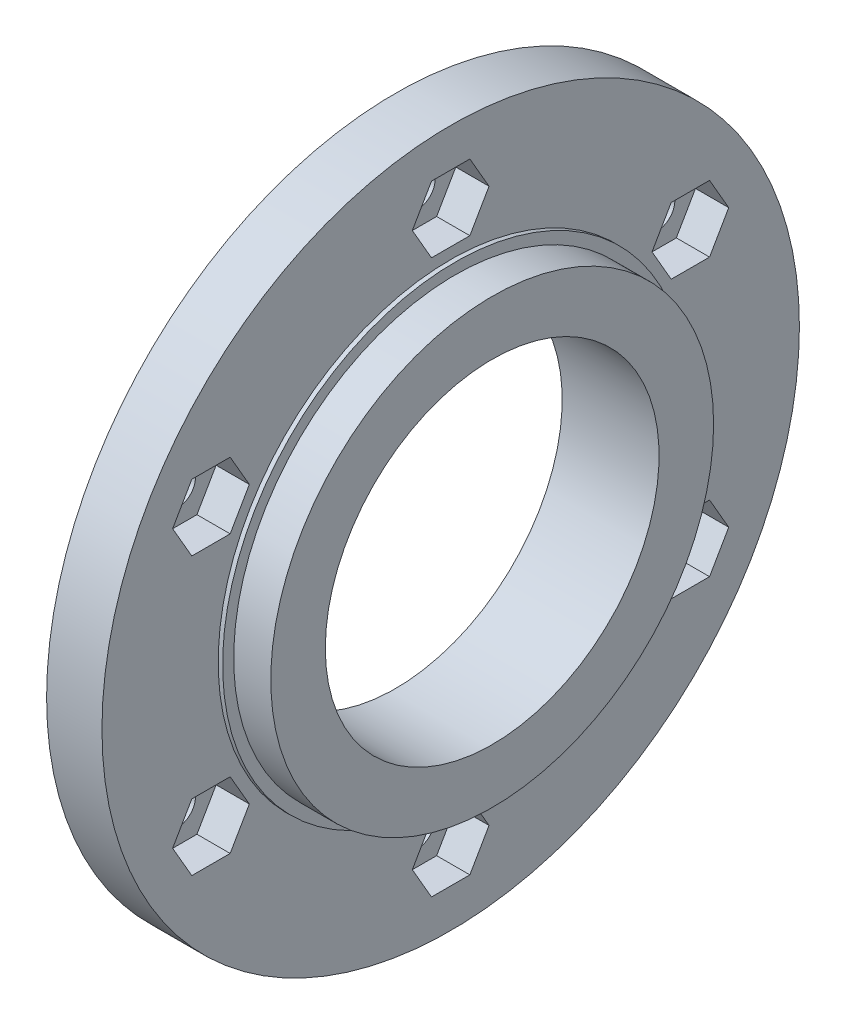
SolidWorks part; units mm, degrees
ref_plane "Ebene vorne" through (0, 0, 0) normal (0, 0, 1) x (1, 0, 0)
ref_plane "Ebene oben" through (0, 0, 0) normal (0, 1, 0) x (1, 0, 0)
ref_plane "Ebene rechts" through (0, 0, 0) normal (1, 0, 0) x (0, 0, -1)
sketch "Skizze1" plane through (0, 0, 0) normal (0, 0, 1) x (1, 0, 0)
  line L0 (0, 0) -> (-40471.317, 0) construction
  line L1 (0, 0) -> (0, 31.5)
  line L2 (0, 31.5) -> (5, 31.5)
  line L3 (5, 31.5) -> (5, 21)
  line L4 (5, 21) -> (5.4, 21)
  line L6 (8.75, 0) -> (0, 0)
  line L7 (8.75, 0) -> (8.75, 20)
  line L8 (8.75, 20) -> (5.4, 20)
  line L9 (5.4, 21) -> (5.4, 20)
  dimension "D1" = 42
  dimension "D2" = 0.4
  dimension "D3" = 3.35
  dimension "D4" = 63
  dimension "D5" = 40
  dimension "D6" = 8.75
revolve "Rotation1" add sketch "Skizze1" angle 360 about L0
sketch "Skizze2" plane through (0, 0, 0) normal (-1, 0, 0) x (0, 0, 1)
  circle A0 centre (0, 0) radius 15.075
  dimension "D1" = 30.15
extrude "Schnitt-Linear austragen1" cut sketch "Skizze2" against normal through all
sketch "Skizze3" plane through (5, 0, 0) normal (1, 0, 0) x (0, 0, -1)
  line L0 (0, 0) -> (0, -50000) construction
  line L2 (1.7321, 22) -> (3.4641, 25)
  line L3 (3.4641, 25) -> (1.7321, 28)
  line L4 (1.7321, 28) -> (-1.7321, 28)
  line L5 (-1.7321, 28) -> (-3.4641, 25)
  line L6 (-3.4641, 25) -> (-1.7321, 22)
  line L7 (-1.7321, 22) -> (1.7321, 22)
  circle A0 centre (0, 25) radius 3 construction
  circle A1 centre (0, 0) radius 25 construction
  dimension "D2" = 50
  dimension "D1" = 6
extrude "Schnitt-Linear austragen2" cut sketch "Skizze3" against normal blind 3
pattern_circular "Kreismuster1" count 6 over 360 about axis through (8.75, 0, 0) along (-1, 0, 0) of "Schnitt-Linear austragen2"
hole_wizard "Ø3.2 (3.2) Durchmesser Bohrung1" positions "Skizze4" profile "Skizze5" hole size "Ø3.2" standard "ISO" end condition through all
sketch "Skizze4" plane through (5, 0, 0) normal (1, 0, 0) x (0, 0, -1)
  line L0 (0, 0) -> (0, -50000) construction
  circle A0 centre (0, 0) radius 25 construction
  point P9 (0, 25)
  dimension "D1" = 50
sketch "Skizze5" plane through (5, 25, 0) normal (0, 1, 0) x (0, 0, -1)
  line L0 (0, 0) -> (0, 5)
  line L1 (0, 5) -> (1.6, 5)
  line L2 (1.6, 5) -> (1.6, 0)
  line L5 (1.6, 0) -> (0, 0)
  line L11 (0, -6.35) -> (0, 107.95) construction
  dimension "Bohrerdurchmesser" = 3.2
  dimension "Bohrungstiefe" = 5
pattern_circular "Kreismuster2" count 6 over 360 about axis through (8.75, 0, 0) along (-1, 0, 0) of "Ø3.2 (3.2) Durchmesser Bohrung1"
